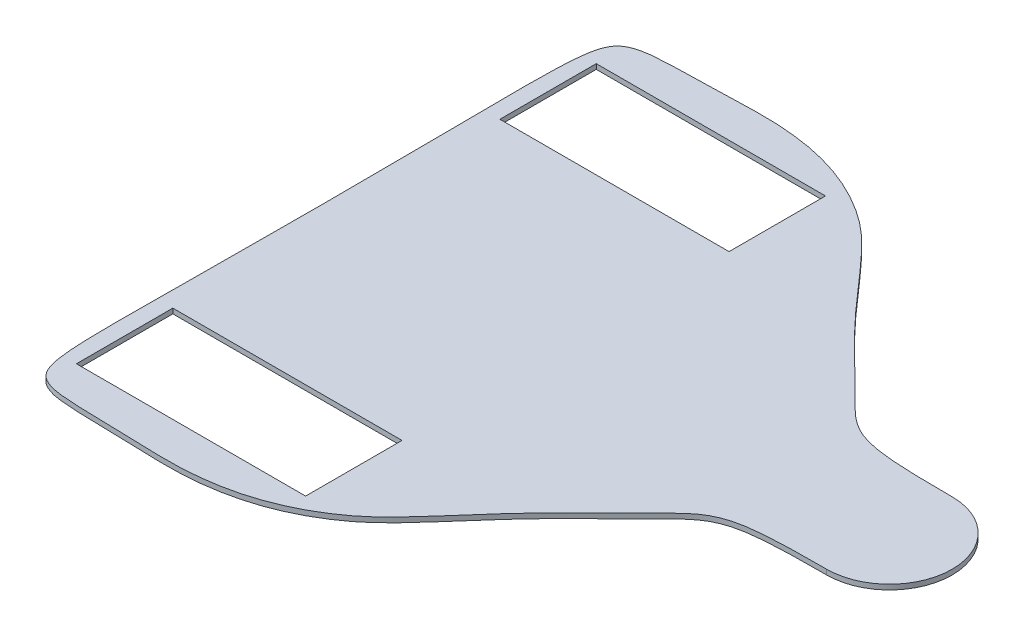
SolidWorks part; units mm, degrees
material "PLA"
ref_plane "Front Plane" through (0, 0, 0) normal (0, 0, 1) x (1, 0, 0)
ref_plane "Top Plane" through (0, 0, 0) normal (0, 1, 0) x (1, 0, 0)
ref_plane "Right Plane" through (0, 0, 0) normal (1, 0, 0) x (0, 0, -1)
sketch "base dimensions" plane through (0, 0, 0) normal (0, 1, 0) x (1, 0, 0)
  line L0 (0, 0) -> (-116.6267, 0) construction
  line L2 (-112.85, 41.1) -> (-112.85, -41.1)
  line L3 (-96.85, 41.1) -> (-96.85, -41.1)
  line L5 (-112.85, 41.1) -> (-96.85, -41.1) construction
  line L6 (-96.85, 41.1) -> (-112.85, -41.1) construction
  line L7 (-131.85, -27.5) -> (-114.85, -27.5)
  line L8 (-131.85, -27.5) -> (-131.85, 27.5)
  line L9 (-114.85, -27.5) -> (-114.85, 27.5)
  line L10 (-131.85, 27.5) -> (-114.85, 27.5)
  line L11 (-131.85, -27.5) -> (-114.85, 27.5) construction
  line L12 (-114.85, -27.5) -> (-131.85, 27.5) construction
  line L13 (-94.85, 0) -> (-94.85, 10.9056)
  line L14 (-135.85, -577.028) -> (-135.85, 577.028) construction
  line L16 (-130.25, -60.15) -> (-79.45, -60.15)
  line L17 (-130.25, 41.1) -> (-79.45, 41.1)
  line L18 (-130.25, 41.1) -> (-130.25, 60.15)
  line L19 (-130.25, 60.15) -> (-79.45, 60.15)
  line L20 (-79.45, 41.1) -> (-79.45, 60.15)
  line L21 (-79.45, -41.1) -> (-79.45, -60.15)
  line L22 (-130.25, -41.1) -> (-79.45, -41.1)
  line L23 (-130.25, -41.1) -> (-130.25, -60.15)
  circle A0 centre (0, 0) radius 63.5 construction
  circle A1 centre (0, 0) radius 15
  circle A2 centre (-81, 0) radius 13.85
  spline S0 degree 3 poles (0, 15) (-26.0597, 15) (-24.2984, 16.8762) (-51.0086, 41.9815) (-61.2896, 55.9447) (-79.9531, 69.6921) (-95.0158, 71.7163) (-110.819, 71.0052) (-126.522, 70.8741) (-138.1428, 68.2179) (-135.85, 61.1511) (-135.85, 0) knots 0 0 0 0 0.141138 0.170317 0.278296 0.317035 0.518967 0.554463 0.636493 0.682072 1 1 1 1
  spline S1 degree 3 poles (0, -15) (-26.0597, -15) (-24.2984, -16.8762) (-51.0086, -41.9815) (-61.2896, -55.9447) (-79.9531, -69.6921) (-95.0158, -71.7163) (-110.819, -71.0052) (-126.522, -70.8741) (-138.1428, -68.2179) (-135.85, -61.1511) (-135.85, 0) knots 0 0 0 0 0.141138 0.170317 0.278296 0.317035 0.518967 0.554463 0.636493 0.682072 1 1 1 1
  point P4 (-96.85, 0)
  point P8 (-67.15, 0)
  point P10 (-104.85, 0)
  point P11 (-63.5, 0)
  point P20 (-123.35, 0)
  point P27 (-114.85, 0)
  point P34 (-56.953, 56.0544)
  point P36 (-106.4691, 70.2739)
  point P38 (-114.1335, 72.5934)
  point P40 (-107.175, 71.1815)
  point P41 (-127.741, 70.4334)
  point P42 (-58.8798, 55.8833)
  point P44 (-37.5588, 39.1722)
  point P45 (-39.5757, 31.2488)
  point P46 (-67.15, 60.15)
  dimension "D1" = 127
  dimension "D2" = 30
  dimension "D5" = 27.7
  dimension "D9" = 2
  dimension "D10" = 81
  dimension "D15" = 90
  dimension "D3" = 82.2
  dimension "D4" = 16
  dimension "D6" = 55
  dimension "D7" = 17
  dimension "D8" = 2
  dimension "D11" = 19.05
  dimension "D12" = 50.8
  dimension "D14" = 3.65
  dimension "D18" = 4
extrude "Boss-Extrude1" add sketch "base dimensions" against normal blind 1.2 contours S1 A1 S0 L23 L22 L2 L17 L18 L19 L20 L3 L21 L16 A2 L8 L10 L9 L7 | L22 L23 L16 L21 | L2 L22 L3 L17 | L10 L8 L7 L9 | L17 L20 L19 L18 | A2 | A1 region at (-104.85, 0, 0) region at (-104.85, 0, -50.625) region at (-104.85, 0, 50.625) region at (-123.35, 0, 0) region at (0, 0, 0) region at (-16.9714, 0, 0) region at (-81, 0, 0)
sketch "Sketch2" plane through (0, -1.2, 0) normal (0, -1, 0) x (-1, 0, 0)
  line L4 (-200000, 0) -> (200116.6267, 0) construction
  line L5 (-200000, 0) -> (200116.6267, 0)
  line L8 (132.25, 39.1) -> (132.25, 62.15)
  line L9 (77.45, 39.1) -> (132.25, 39.1)
  line L10 (77.45, 62.15) -> (77.45, 39.1)
  line L11 (132.25, 62.15) -> (77.45, 62.15)
  line L12 (132.25, 39.1) -> (132.25, 62.15)
  line L13 (77.45, 39.1) -> (132.25, 39.1)
  line L14 (77.45, 62.15) -> (77.45, 39.1)
  line L15 (132.25, 62.15) -> (77.45, 62.15)
  line L22 (77.45, -62.15) -> (132.25, -62.15)
  line L23 (77.45, -39.1) -> (77.45, -62.15)
  line L24 (132.25, -39.1) -> (77.45, -39.1)
  line L25 (132.25, -62.15) -> (132.25, -39.1)
  line L26 (77.45, -62.15) -> (132.25, -62.15)
  line L27 (77.45, -39.1) -> (77.45, -62.15)
  line L28 (132.25, -39.1) -> (77.45, -39.1)
  line L29 (132.25, -62.15) -> (132.25, -39.1)
  dimension "D1" = 2
  dimension "D2" = 2
extrude "Cut-Extrude1" cut sketch "Sketch2" against normal through all
